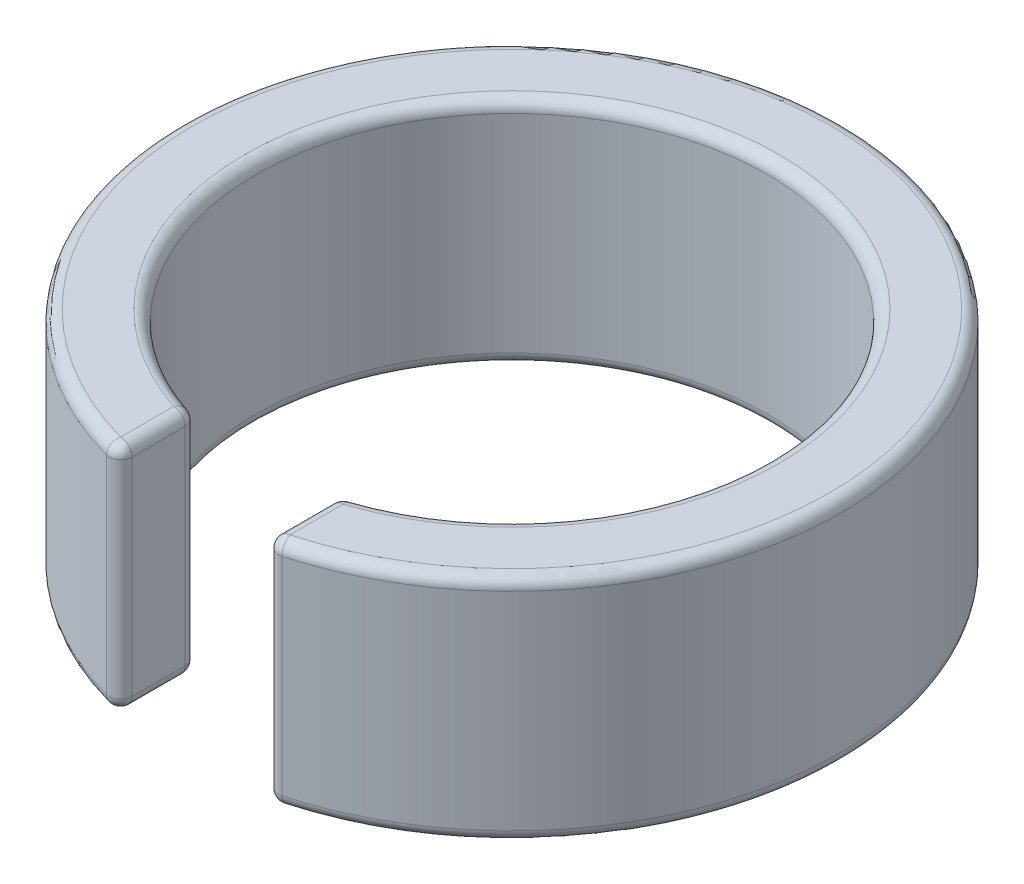
SolidWorks part; units mm, degrees
ref_plane "Front Plane" through (0, 0, 0) normal (0, 0, 1) x (1, 0, 0)
ref_plane "Bottom Plane" through (0, 0, 0) normal (0, 1, 0) x (1, 0, 0)
ref_plane "Mid ZY Plane" through (0, 0, 0) normal (1, 0, 0) x (0, 0, -1)
ref_axis "X Axis" through (-15.73, 0, 0) along (1, 0, 0)
ref_axis "Y Axis" through (0, 10.5, 0) along (0, -1, 0)
ref_axis "Z Axis" through (0, 0, -15.7088) along (0, 0, 1)
sketch "Labels" plane through (0, 0, 0) normal (0, 0, 1) x (1, 0, 0)
  line L0 (-609.6, 609.6) -> (609.6, 609.6)
  line L1 (0, 609.6) -> (0, 0)
  text T0 "CANTI STOP SHIM-Material <not specified>-QTY(($EvalError$))" font "Arial" height 38.1
  dimension "D1" = 609.6
  dimension "D2" = 1219.2
sketch "Sketch1" plane through (0, 0, 0) normal (0, 1, 0) x (1, 0, 0)
  circle A0 centre (0, 0) radius 11.1
  circle A1 centre (0, 0) radius 14.3
  dimension "D1" = 22.2
  dimension "D2" = 28.6
extrude "Boss-Extrude1" add sketch "Sketch1" along normal blind 10
sketch "Sketch2" plane through (0, 0, 0) normal (0, 1, 0) x (1, 0, 0)
  line L1 (-3.175, 0) -> (3.175, 0)
  line L2 (-3.175, 0) -> (-3.175, -14.3)
  line L3 (-3.175, -14.3) -> (3.175, -14.3)
  line L4 (3.175, 0) -> (3.175, -14.3)
  circle A0 centre (0, 0) radius 14.3 construction
  dimension "D1" = 6.35
extrude "Cut-Extrude1" cut sketch "Sketch2" along normal through all
fillet "Fillet1" radius 0.5 12 edges at (0, 0, -11.1) (3.175, 0, 12.2897) (0, 0, -14.3) (-3.175, 0, 12.2897) (3.175, 10, 12.2897) (0, 10, -11.1) (-3.175, 10, 12.2897) (0, 10, -14.3) (3.175, 5, 10.6362) (3.175, 5, 13.9431) (-3.175, 5, 10.6362) (-3.175, 5, 13.9431)
